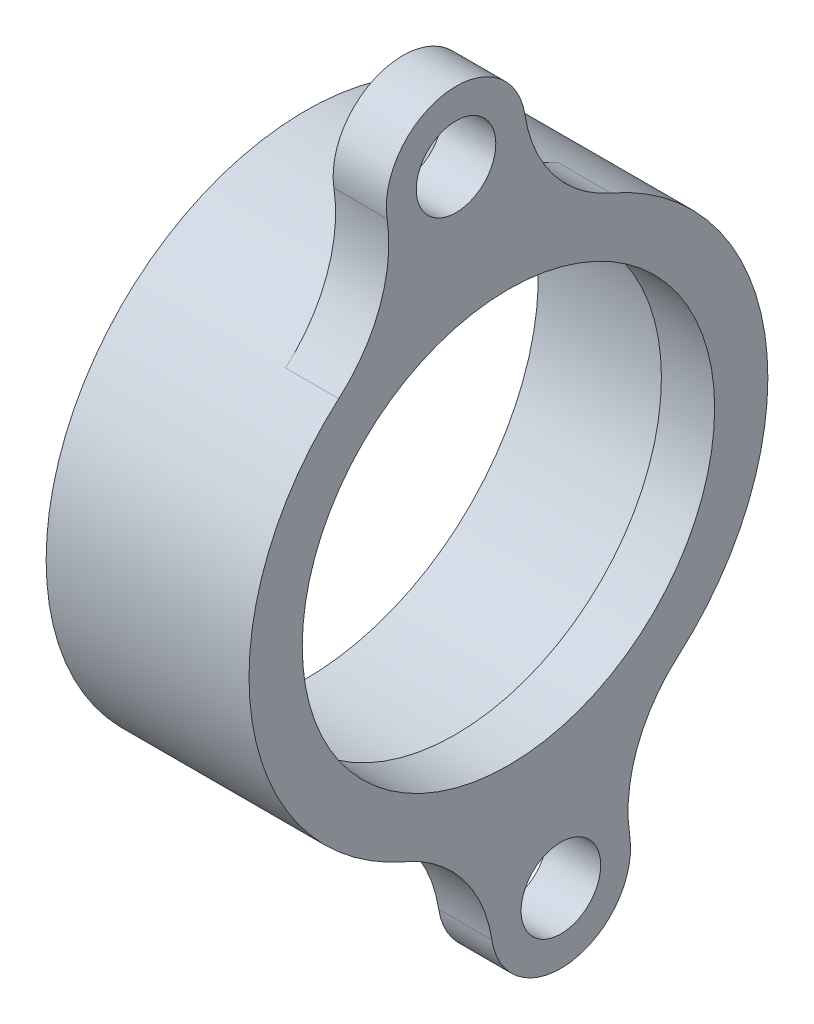
SolidWorks part; units mm, degrees
ref_plane "Front Plane" through (0, 0, 0) normal (0, 0, 1) x (1, 0, 0)
ref_plane "Top Plane" through (0, 0, 0) normal (0, 1, 0) x (1, 0, 0)
ref_plane "Right Plane" through (0, 0, 0) normal (1, 0, 0) x (0, 0, -1)
sketch "Sketch1" plane through (0, 0, 0) normal (0, 0, 1) x (1, 0, 0)
  line L0 (30.9563, 12.3825) -> (38.1, 12.3825)
  line L1 (38.1, 12.3825) -> (38.1, 11.1125)
  line L2 (38.1, 11.1125) -> (30.9563, 11.1125)
  line L4 (30.9563, 11.1125) -> (30.9563, 12.3825)
  line L5 (0, 0) -> (40.0174, 0) construction
  dimension "D1" = 1.27
  dimension "D2" = 7.1437
revolve "Revolve1" add sketch "Sketch1" angle 360 about L5
sketch "Sketch2" plane through (38.1, 0, 0) normal (1, 0, 0) x (0, 0, -1)
  line L0 (3.6897, -23.8296) -> (-3.6897, 23.8296) construction
  line L1 (-5.7902, 15.6496) -> (0.7862, 16.6678) construction
  line L2 (-11.4911, -1.7793) -> (11.4911, 1.7793) construction
  line L4 (-4.1591, 11.8861) -> (0.3697, 12.5873) construction
  line L5 (0.3697, 12.5873) -> (2.0268, 16.8599) construction
  line L6 (2.0268, 16.8599) -> (-0.8449, 20.4313) construction
  line L7 (-0.8449, 20.4313) -> (-5.3736, 19.7301) construction
  line L8 (-5.3736, 19.7301) -> (-7.0307, 15.4575) construction
  line L9 (-7.0307, 15.4575) -> (-4.1591, 11.8861) construction
  arc A0 (-8.0987, 9.3668) -> (-4.8868, -11.3774) centre (0, 0) ccw
  circle A1 centre (0, 0) radius 12.3825 construction
  arc A7 (0.7862, 16.6678) -> (-5.7902, 15.6496) centre (-2.502, 16.1587) ccw
  arc A8 (-8.0987, 9.3668) -> (-5.7902, 15.6496) centre (-12.617, 14.5925) ccw
  arc A9 (0.7862, 16.6678) -> (4.8868, 11.3774) centre (7.6131, 17.7249) ccw
  circle A10 centre (0, 0) radius 9.8425
  circle A11 centre (0, 0) radius 11.1125 construction
  arc A12 (5.7902, -15.6496) -> (8.0987, -9.3668) centre (12.617, -14.5925) cw
  arc A14 (5.7902, -15.6496) -> (-0.7862, -16.6678) centre (2.502, -16.1587) cw
  arc A15 (-4.8868, -11.3774) -> (-0.7862, -16.6678) centre (-7.6131, -17.7249) cw
  arc A16 (8.0987, -9.3668) -> (4.8868, 11.3774) centre (0, 0) ccw
  circle A17 centre (-2.502, 16.1587) radius 3.9688 construction
  arc A18 (1.5403, 20.0021) -> (-7.5172, 18.5996) centre (-2.9885, 19.3009) ccw construction
  arc A19 (-1.5403, -20.0021) -> (7.5172, -18.5996) centre (2.9885, -19.3009) ccw construction
  point P6 (0, 21.8442)
  dimension "D1" = 1.27
  dimension "D2" = 3.3274
  dimension "D3" = 7.9375
extrude "Boss-Extrude1" add sketch "Sketch2" along normal blind 2.54
hole_wizard "#6 Clearance Hole1" positions "Sketch3" profile "Sketch5" hole size "#6" standard "ANSI Inch" end condition up to next
sketch "Sketch3" plane through (40.64, 0, 0) normal (1, 0, 0) x (0, 0, -1)
  point P0 (-2.502, 16.1587)
  point P3 (2.502, -16.1587)
sketch "Sketch5" plane through (40.64, 16.1587, 2.502) normal (0, 1, 0) x (0, 0, -1)
  line L0 (0, 0) -> (0, 2.54)
  line L1 (0, 2.54) -> (1.8986, 2.54)
  line L2 (1.8986, 2.54) -> (1.8986, 0)
  line L5 (1.8986, 0) -> (0, 0)
  line L11 (0, -6.35) -> (0, 107.95) construction
  dimension "Thru Hole Dia." = 3.7973
  dimension "Thru Hole Depth" = 2.54
